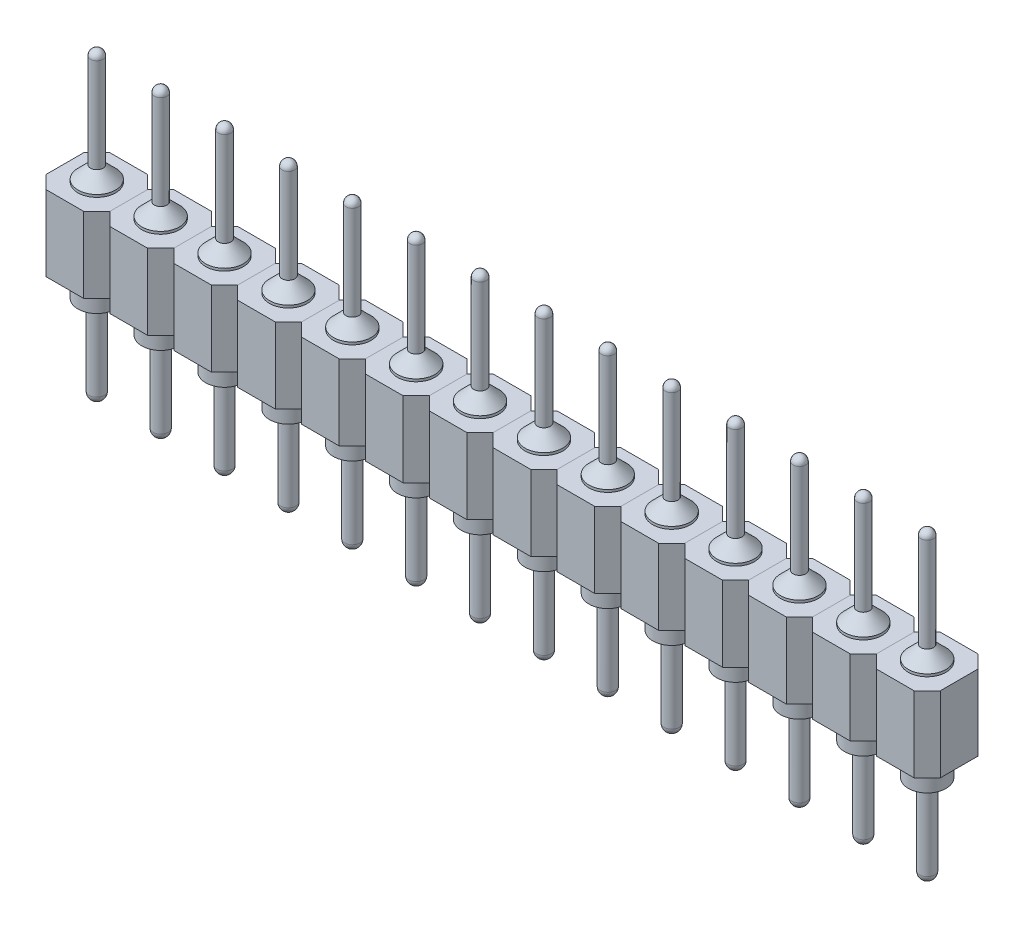
SolidWorks part; units mm, degrees
ref_plane "Спереди" through (0, 0, 0) normal (0, 0, 1) x (1, 0, 0)
ref_plane "Сверху" through (0, 0, 0) normal (0, 1, 0) x (1, 0, 0)
ref_plane "Справа" through (0, 0, 0) normal (1, 0, 0) x (0, 0, -1)
other "Configuration Table"
sketch "Эскиз2" plane through (0, 0, 0) normal (0, 0, 1) x (1, 0, 0)
  line L0 (0, 12.1) -> (0, 0) construction
  line L1 (0, 0) -> (0, 12.1)
  line L2 (0.3, 0.3) -> (0.3, 3.5)
  line L3 (0.3, 3.5) -> (0.75, 3.5)
  line L4 (0.75, 3.5) -> (0.75, 7.6)
  line L5 (0.25, 11.85) -> (0.25, 8.1)
  line L6 (0.25, 8.1) -> (0.75, 7.6)
  circle A0 centre (0, 11.85) radius 0.25
  circle A1 centre (0, 0.3) radius 0.3
  dimension "D1" = 0.5
  dimension "D2" = 0.6
  dimension "D3" = 4
  dimension "D4" = 0.5
  dimension "D5" = 4.1
  dimension "D6" = 3.5
  dimension "D7" = 0.75
revolve "Повернуть1" add sketch "Эскиз2" angle 360 about L1
sketch "Эскиз3" plane through (0, 3.5, 0) normal (0, -1, 0) x (1, 0, 0)
  line L0 (0, 1.27) -> (0, -1.27) construction
  line L1 (-0.75, 1.27) -> (0.75, 1.27)
  line L2 (-1.27, 0.75) -> (-1.27, -0.75)
  line L3 (-0.75, -1.27) -> (0.75, -1.27)
  line L4 (1.27, 0.75) -> (1.27, -0.75)
  line L5 (-1.27, 0.75) -> (-0.75, 1.27)
  line L6 (0.75, 1.27) -> (1.27, 0.75)
  line L7 (0.75, -1.27) -> (1.27, -0.75)
  line L8 (-1.27, -0.75) -> (-0.75, -1.27)
  circle A0 centre (0, 0) radius 0.75
  point P0 (-1.27, 1.27)
  point P1 (1.27, -1.27)
  point P2 (-1.27, -1.27)
  point P3 (1.27, 1.27)
  dimension "D2" = 1.5
  dimension "D1" = 2.54
  dimension "D3" = 2.54
extrude "Бобышка-Вытянуть1" add sketch "Эскиз3" against normal blind 3 from offset 1 separate body offset against normal yes
pattern_linear "Линейный массив1" count 14 spacing 2.54 along (-1, 0, 0) of bodies 104 103
